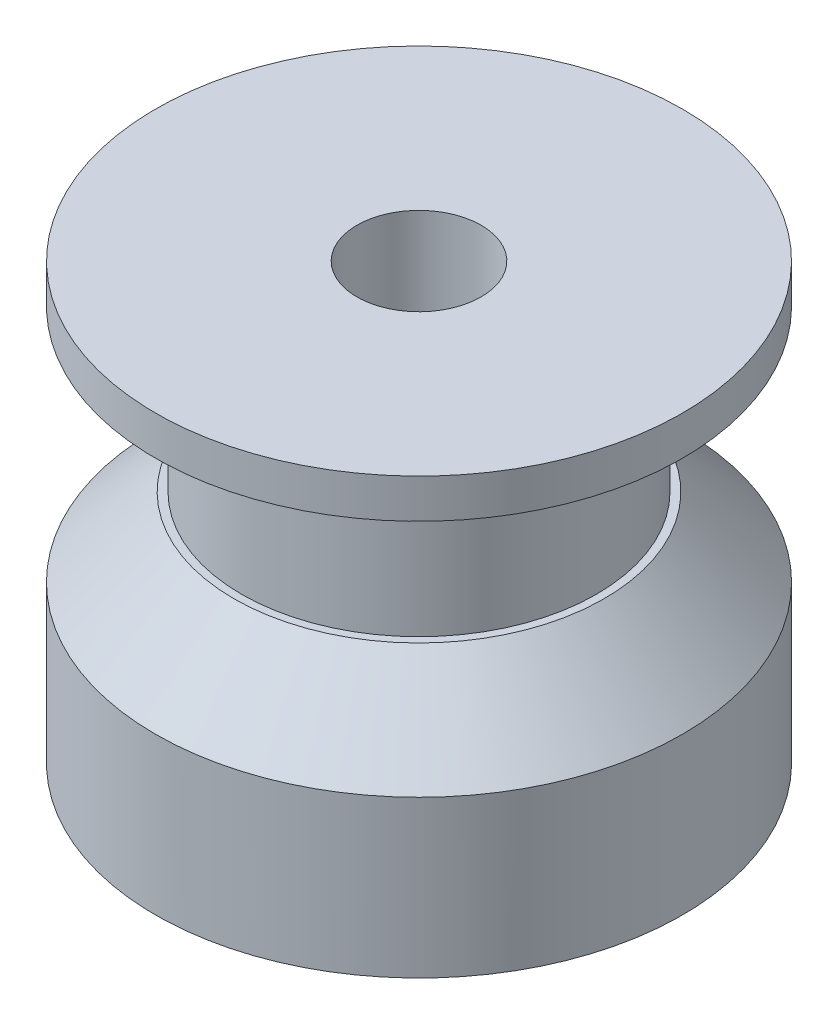
SolidWorks part; units mm, degrees
material "6061 Alloy"
ref_plane "Front Plane" through (0, 0, 0) normal (0, 0, 1) x (1, 0, 0)
ref_plane "Top Plane" through (0, 0, 0) normal (0, 1, 0) x (1, 0, 0)
ref_plane "Right Plane" through (0, 0, 0) normal (1, 0, 0) x (0, 0, -1)
sketch "Sketch1" plane through (0, 0, 0) normal (0, 0, 1) x (1, 0, 0)
  line L0 (0, 0) -> (0, 16.6392) construction
  line L1 (0, 0) -> (31.4533, 0) construction
  line L2 (1.5875, 0) -> (1.5875, 11.1054)
  line L3 (1.5875, 11.1054) -> (6.73, 11.1054)
  line L4 (6.73, 11.1054) -> (6.73, 10.1054)
  line L5 (6.73, 10.1054) -> (4.535, 10.1054)
  line L6 (4.535, 10.1054) -> (4.535, 6)
  line L7 (4.535, 6) -> (6.731, 6)
  line L8 (6.731, 6) -> (6.731, 0)
  line L9 (6.731, 0) -> (1.5875, 0)
  dimension "D1" = 6.731
  dimension "D2" = 1.5875
  dimension "D3" = 6
  dimension "D4" = 1
  dimension "D5" = 5.1054
  dimension "D6" = 4.535
  dimension "D7" = 6.73
revolve "Revolve1" add sketch "Sketch1" angle 360 about L0
chamfer "Chamfer1" distance 2 angle 45 1 edges at (0, 6, -6.731)
